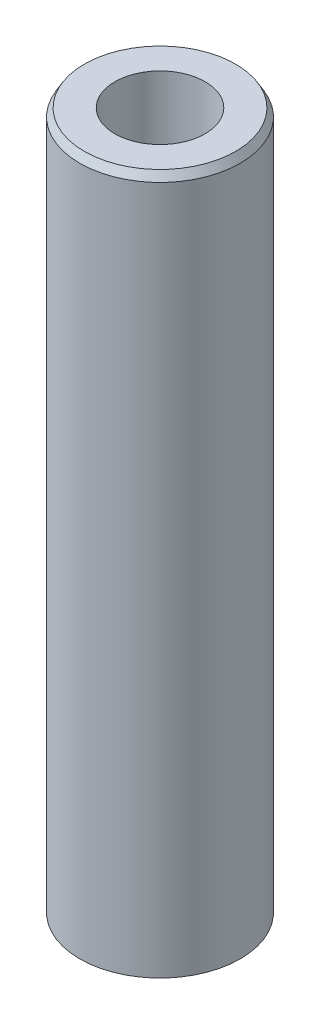
SolidWorks part; units mm, degrees
ref_plane "Front Plane" through (0, 0, 0) normal (0, 0, 1) x (1, 0, 0)
ref_plane "Top Plane" through (0, 0, 0) normal (0, 1, 0) x (1, 0, 0)
ref_plane "Right Plane" through (0, 0, 0) normal (1, 0, 0) x (0, 0, -1)
sketch "Sketch1" plane through (0, 0, 0) normal (0, 1, 0) x (1, 0, 0)
  circle A0 centre (0, 0) radius 40
  dimension "SHAFT_OD" = 80
extrude "Boss-Extrude1" add sketch "Sketch1" along normal blind 349.7177
sketch "Sketch2" plane through (0, 0, 0) normal (0, 1, 0) x (1, 0, 0)
  circle A0 centre (0, 0) radius 22.4991
  dimension "BORE_D" = 44.9983
extrude "Cut-Extrude1" cut sketch "Sketch2" along normal through all
chamfer "Chamfer1" distance 3.9789 angle 30 2 edges at (0, 349.7177, 40) (0, 0, 40) first distance on face at (0, 349.7177, 40) first distance on face at (0, 0, 22.4991)
